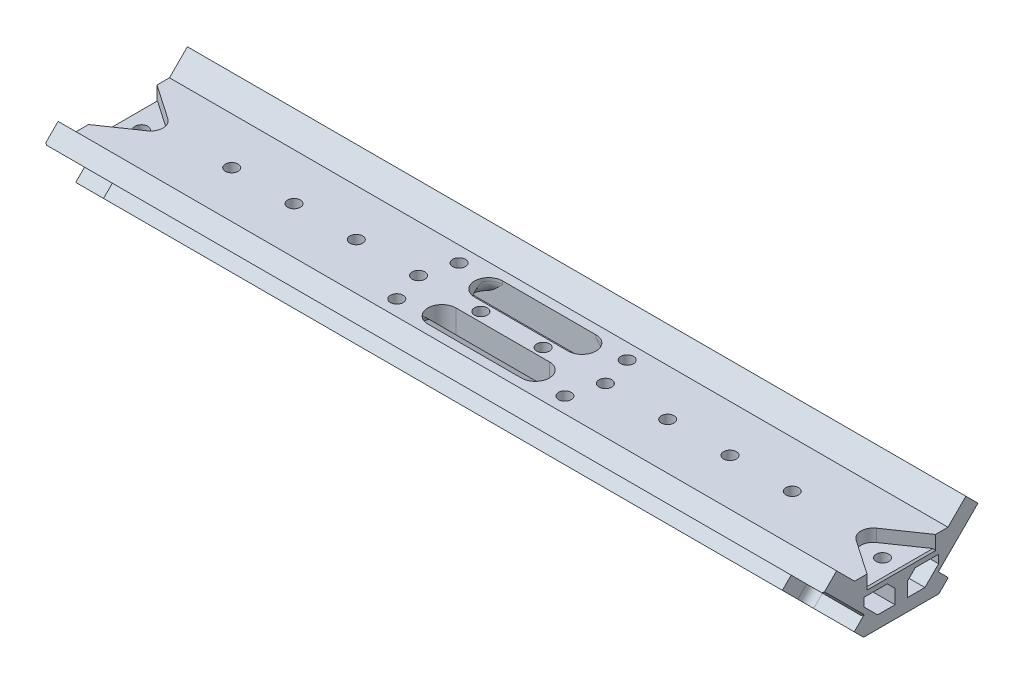
SolidWorks part; units mm, degrees
ref_plane "Front Plane" through (0, 0, 0) normal (0, 0, 1) x (1, 0, 0)
ref_plane "Top Plane" through (0, 0, 0) normal (0, 1, 0) x (1, 0, 0)
ref_plane "Right Plane" through (0, 0, 0) normal (1, 0, 0) x (0, 0, -1)
sketch "Sketch1" plane through (0, 0, 0) normal (1, 0, 0) x (0, 0, -1)
  line L1 (-25, 0) -> (25, 0)
  line L2 (-25, 0) -> (-25, 30)
  line L3 (-25, 30) -> (25, 30)
  line L4 (25, 0) -> (25, 30)
  dimension "D1" = 30
  dimension "D2" = 50
  dimension "D3" = 25
extrude "Boss-Extrude1" add sketch "Sketch1" along normal blind 125 and the other way blind 125
sketch "Sketch2" plane through (125, 0, 0) normal (1, 0, 0) x (0, 0, -1)
  line L0 (-10, 0) -> (-25, 15)
  line L1 (-25, 0) -> (25, 0) construction
  line L2 (-25, 30) -> (-25, 0) construction
  line L3 (-25, 15) -> (-25, 0)
  line L4 (-25, 0) -> (-10, 0)
  line L5 (25, 15) -> (10, 0)
  line L6 (25, 0) -> (25, 30) construction
  line L7 (10, 0) -> (25, 0)
  line L8 (25, 0) -> (25, 15)
  dimension "D1" = 15
  dimension "D2" = 15
  dimension "D3" = 15
  dimension "D4" = 15
extrude "Cut-Extrude1" cut sketch "Sketch2" against normal through all
sketch "Sketch4" plane through (125, 0, 0) normal (1, 0, 0) x (0, 0, -1)
  line L8 (-22.1716, 12.1716) -> (-19.3431, 15)
  line L9 (-10, 0) -> (-25, 15) construction
  line L10 (-19.3431, 15) -> (-25, 20.6569)
  line L11 (-25, 30) -> (-25, 15) construction
  line L12 (-25, 20.6569) -> (-25, 15)
  line L13 (-25, 15) -> (-22.1716, 12.1716)
  line L14 (22.1716, 12.1716) -> (19.3431, 15)
  line L15 (25, 15) -> (10, 0) construction
  line L16 (19.3431, 15) -> (25, 20.6569)
  line L17 (25, 15) -> (25, 30) construction
  line L18 (25, 20.6569) -> (25, 15)
  line L19 (25, 15) -> (22.1716, 12.1716)
  dimension "D1" = 4
  dimension "D2" = 4
  dimension "D3" = 8
  dimension "D4" = 8
extrude "Cut-Extrude2" cut sketch "Sketch4" against normal through all
sketch "Sketch5" plane through (125, 0, 0) normal (1, 0, 0) x (0, 0, -1)
  line L0 (-25, 20.6569) -> (-20.7574, 24.8995)
  line L1 (-20.7574, 24.8995) -> (-15, 19.1421)
  line L2 (-15, 19.1421) -> (15, 19.1421)
  line L3 (15, 19.1421) -> (20.7574, 24.8995)
  line L4 (20.7574, 24.8995) -> (25, 20.6569)
  line L5 (25, 20.6569) -> (25, 30)
  line L6 (25, 30) -> (-25, 30)
  line L7 (-25, 30) -> (-25, 20.6569)
  line L8 (25, 20.6569) -> (19.3431, 15) construction
  point P6 (20.5583, 24.6906)
  point P18 (-20.7574, 24.8995)
  dimension "D1" = 6
  dimension "D2" = 6
  dimension "D3" = 30
  dimension "D4" = 15
extrude "Cut-Extrude3" cut sketch "Sketch5" against normal through all
sketch "Sketch6" plane through (0, 19.1421, 0) normal (0, 1, 0) x (1, 0, 0)
  circle A0 centre (-10, 0) radius 2.05
  circle A1 centre (10, 0) radius 2.05
  circle A2 centre (30, 0) radius 2.05
  circle A3 centre (50, 0) radius 2.05
  circle A4 centre (70, 0) radius 2.05
  circle A5 centre (90, 0) radius 2.05
  circle A6 centre (-30, 0) radius 2.05
  circle A7 centre (-50, 0) radius 2.05
  circle A8 centre (-70, 0) radius 2.05
  circle A9 centre (-90, 0) radius 2.05
  dimension "D1" = 4.1
  dimension "D2" = 20
  dimension "D3" = 10
  dimension "D4" = 20
  dimension "D5" = 20
  dimension "D6" = 20
  dimension "D7" = 20
  dimension "D8" = 20
  dimension "D9" = 20
  dimension "D10" = 20
  dimension "D11" = 20
extrude "Cut-Extrude4" cut sketch "Sketch6" against normal blind 6
sketch "Sketch7" plane through (-125, 0, 0) normal (-1, 0, 0) x (0, 0, 1)
  line L0 (-8.3431, 4) -> (-2, 4)
  line L1 (8.3431, 4) -> (14.9902, 10.647)
  line L3 (10.4951, 15.1421) -> (6.4951, 15.1421)
  line L5 (-14.9902, 10.647) -> (-8.3431, 4)
  line L6 (10, 0) -> (22.1716, 12.1716) construction
  line L7 (-22.1716, 12.1716) -> (-10, 0) construction
  line L8 (10, 0) -> (-10, 0) construction
  line L9 (-2, 10.647) -> (-2, 4)
  line L10 (2, 10.647) -> (2, 4)
  line L11 (-6.4951, 15.1421) -> (-10.4951, 15.1421)
  line L12 (2, 4) -> (8.3431, 4)
  line L13 (-6.4951, 15.1421) -> (-2, 10.647)
  line L14 (-14.9902, 10.647) -> (-10.4951, 15.1421)
  line L15 (14.9902, 10.647) -> (10.4951, 15.1421)
  line L16 (6.4951, 15.1421) -> (2, 10.647)
  line L17 (15, 19.1421) -> (-15, 19.1421) construction
  point P2 (0, 0)
  point P4 (0, 0)
  point P12 (14.8624, 10.5192)
  point P13 (-6.2846, 15.1421)
  point P25 (14.3409, 9.9978)
  dimension "D1" = 2
  dimension "D2" = 4
  dimension "D3" = 4
  dimension "D4" = 4
  dimension "D5" = 90
  dimension "D6" = 90
  dimension "D7" = 2
  dimension "D8" = 135
  dimension "D9" = 4
  dimension "D10" = 4
extrude "Cut-Extrude5" cut sketch "Sketch7" against normal through all
sketch "Sketch8" plane through (-125, 0, 0) normal (-1, 0, 0) x (0, 0, 1)
  line L0 (-12, 13.6372) -> (-12, 7.6569)
  line L1 (-10.4951, 15.1421) -> (-14.9902, 10.647) construction
  line L2 (-14.9902, 10.647) -> (-8.3431, 4) construction
  line L3 (-12, 7.6569) -> (-14.9902, 10.647)
  line L4 (-14.9902, 10.647) -> (-12, 13.6372)
  line L5 (12, 13.6372) -> (12, 7.6569)
  line L6 (14.9902, 10.647) -> (10.4951, 15.1421) construction
  line L7 (8.3431, 4) -> (14.9902, 10.647) construction
  line L8 (12, 7.6569) -> (14.9902, 10.647)
  line L9 (14.9902, 10.647) -> (12, 13.6372)
  point P6 (0, 0)
  dimension "D1" = 12
extrude "Boss-Extrude2" add sketch "Sketch8" against normal through all
sketch "Sketch9" plane through (125, 0, 0) normal (1, 0, 0) x (0, 0, -1)
  line L0 (-16.0858, 6.0858) -> (16.0858, 6.0858)
  line L1 (-10, 0) -> (-22.1716, 12.1716) construction
  line L2 (22.1716, 12.1716) -> (10, 0) construction
  line L3 (16.0858, 6.0858) -> (10, 0)
  line L4 (10, 0) -> (-10, 0)
  line L5 (-10, 0) -> (-16.0858, 6.0858)
extrude "Boss-Extrude3" add sketch "Sketch9" against normal through all
sketch "Sketch10" plane through (125, 0, 0) normal (1, 0, 0) x (0, 0, -1)
  line L0 (-12.0858, 2.0858) -> (12.0858, 2.0858)
  line L1 (-10, 0) -> (-22.1716, 12.1716) construction
  line L2 (22.1716, 12.1716) -> (10, 0) construction
  line L3 (12.0858, 2.0858) -> (10, 0)
  line L4 (10, 0) -> (-10, 0)
  line L5 (-10, 0) -> (-12.0858, 2.0858)
  line L6 (-2, 6.0858) -> (-10.4289, 6.0858) construction
  dimension "D1" = 4
extrude "Cut-Extrude6" cut sketch "Sketch10" against normal through all
sketch "Sketch11" plane through (0, -5, 5) normal (0, -0.7071, 0.7071) x (1, 0, 0)
  line L0 (125, 14.2843) -> (109, 14.2843)
  line L1 (125, 10.0208) -> (125, 24.2843) construction
  line L2 (109, 14.2843) -> (109, 24.2843)
  line L3 (-125, 24.2843) -> (125, 24.2843) construction
  line L4 (109, 24.2843) -> (125, 24.2843)
  line L5 (125, 24.2843) -> (125, 14.2843)
  line L6 (-125, 10.0208) -> (-125, 24.2843) construction
  line L7 (-125, 14.2843) -> (-109, 14.2843)
  line L8 (-125, 14.2843) -> (-125, 24.2843)
  line L9 (-125, 24.2843) -> (-109, 24.2843)
  line L10 (-109, 14.2843) -> (-109, 24.2843)
  line L11 (-125, 24.2843) -> (125, 24.2843) construction
  point P17 (0, 0)
  dimension "D1" = 10
  dimension "D2" = 16
  dimension "D3" = 16
extrude "Cut-Extrude7" cut sketch "Sketch11" against normal up to surface (4 mm away) up to face at (0, 17.8284, 22.1716)
sketch "Sketch12" plane through (0, -5, -5) normal (0, -0.7071, -0.7071) x (-1, 0, 0)
  line L13 (125, 32.2843) -> (-125, 32.2843) construction
  line L18 (-125, 14.2843) -> (-109, 14.2843)
  line L19 (-125, 14.2843) -> (-125, 32.2843)
  line L20 (-125, 32.2843) -> (-109, 32.2843)
  line L21 (-109, 14.2843) -> (-109, 32.2843)
  line L23 (125, 14.2843) -> (109, 14.2843)
  line L24 (125, 14.2843) -> (125, 32.2843)
  line L25 (125, 32.2843) -> (109, 32.2843)
  line L26 (109, 14.2843) -> (109, 32.2843)
  point P15 (0, 0)
  point P18 (-106.5228, 15.2998)
  point P19 (-125, 15.2998)
  point P20 (0, 0)
  point P21 (125, 32.2843)
  point P23 (-125, 32.2843)
  dimension "D1" = 10
  dimension "D2" = 16
  dimension "D3" = 16
extrude "Cut-Extrude11" cut sketch "Sketch12" against normal up to surface (4 mm away) up to face at (0, 17.8284, -22.1716)
sketch "Sketch13" plane through (125, 0, 0) normal (1, 0, 0) x (0, 0, -1)
  line L0 (7.6005, 6.0858) -> (13.5147, 12)
  line L1 (10.4289, 6.0858) -> (2, 6.0858) construction
  line L2 (13.5147, 12) -> (14.9289, 10.5858)
  line L3 (12.2721, 7.9289) -> (19.3431, 15) construction
  line L4 (14.9289, 10.5858) -> (10.4289, 6.0858)
  line L5 (10.4289, 6.0858) -> (7.6005, 6.0858)
  line L6 (-7.6005, 6.0858) -> (-13.5147, 12)
  line L7 (-2, 6.0858) -> (-10.4289, 6.0858) construction
  line L8 (-13.5147, 12) -> (-14.9289, 10.5858)
  line L9 (-19.3431, 15) -> (-12.2721, 7.9289) construction
  line L10 (-14.9289, 10.5858) -> (-10.4289, 6.0858)
  line L11 (-10.4289, 6.0858) -> (-7.6005, 6.0858)
  point P13 (0, 0)
  dimension "D1" = 2
  dimension "D2" = 2
  dimension "D3" = 12
extrude "Boss-Extrude4" add sketch "Sketch13" against normal through all
sketch "Sketch14" plane through (0, 19.1421, 0) normal (0, 1, 0) x (1, 0, 0)
  line L13 (125, 11) -> (109, 0)
  line L14 (125, -15) -> (125, 15) construction
  line L15 (109, 0) -> (125, -11)
  line L16 (125, -11) -> (125, 11)
  line L17 (-125, 11) -> (-109, 0)
  line L18 (-125, -15) -> (-125, 15) construction
  line L19 (-109, 0) -> (-125, -11)
  line L20 (-125, -11) -> (-125, 11)
  point P10 (-125, -8.6578)
  point P13 (0, 0)
  point P16 (0, 0)
  dimension "D1" = 4
  dimension "D2" = 4
  dimension "D3" = 16
extrude "Cut-Extrude12" cut sketch "Sketch14" against normal blind 4
sketch "Sketch15" plane through (-125, 0, 0) normal (-1, 0, 0) x (0, 0, 1)
  line L1 (-15, 15.1421) -> (15, 15.1421)
  line L2 (-15, 15.1421) -> (-15, 13.1421)
  line L3 (-15, 13.1421) -> (15, 13.1421)
  line L4 (15, 15.1421) -> (15, 13.1421)
  point P5 (0, 0)
  point P6 (-13.7129, 15.1683)
  dimension "D1" = 2
  dimension "D2" = 4
  dimension "D3" = 30
  dimension "D4" = 15
extrude "Boss-Extrude5" add sketch "Sketch15" against normal through all
fillet "Fillet1" radius 4 2 edges at (109, 17.1421, 0) (-109, 17.1421, 0)
fillet "Fillet2" radius 3 4 edges at (109, 6.5147, -13.6863) (-109, 6.5147, -13.6863) (-109, 6.5147, 13.6863) (109, 6.5147, 13.6863)
sketch "Sketch16" plane through (0, 15.1421, 0) normal (0, 1, 0) x (1, 0, 0)
  circle A0 centre (119, 0) radius 2.05
  circle A1 centre (-119, 0) radius 2.05
  point P4 (0, 0)
  dimension "D1" = 4.1
  dimension "D2" = 6
  dimension "D3" = 6
extrude "Cut-Extrude13" cut sketch "Sketch16" against normal blind 6
sketch "Sketch17" plane through (0, -2.1716, -2.1716) normal (0, -0.7071, -0.7071) x (-1, 0, 0)
  circle A0 centre (-115, 19.2843) radius 2.05
  circle A1 centre (115, 19.2843) radius 2.05
  point P4 (0, 0)
  dimension "D1" = 4.1
  dimension "D2" = 5
  dimension "D3" = 10
  dimension "D4" = 10
extrude "Cut-Extrude14" cut sketch "Sketch17" against normal blind 6
sketch "Sketch18" plane through (0, -2.1716, 2.1716) normal (0, -0.7071, 0.7071) x (1, 0, 0)
  circle A0 centre (-115, 19.2843) radius 2.05
  circle A1 centre (115, 19.2843) radius 2.05
  point P4 (0, 0)
  dimension "D1" = 4.1
  dimension "D2" = 10
  dimension "D3" = 10
  dimension "D4" = 5
extrude "Cut-Extrude15" cut sketch "Sketch18" against normal blind 6
sketch "Sketch19" plane through (0, -2.1716, -2.1716) normal (0, -0.7071, -0.7071) x (-1, 0, 0)
  circle A0 centre (0, 29.2843) radius 2.05
  circle A1 centre (-60, 29.2843) radius 2.05
  circle A2 centre (-120, 29.2843) radius 2.05
  circle A3 centre (60, 29.2843) radius 2.05
  circle A4 centre (120, 29.2843) radius 2.05
  point P10 (0, 0)
  point P11 (0, 0)
  dimension "D1" = 4.1
  dimension "D2" = 3
  dimension "D3" = 60
  dimension "D4" = 60
  dimension "D5" = 60
  dimension "D6" = 60
extrude "Cut-Extrude16" cut sketch "Sketch19" against normal blind 4
sketch "Sketch20" plane through (0, -2.1716, 2.1716) normal (0, -0.7071, 0.7071) x (1, 0, 0)
  circle A0 centre (0, 29.2843) radius 2.05
  circle A1 centre (60, 29.2843) radius 2.05
  circle A2 centre (120, 29.2843) radius 2.05
  circle A3 centre (-60, 29.2843) radius 2.05
  circle A4 centre (-120, 29.2843) radius 2.05
  point P10 (0, 0)
  point P13 (0, 0)
  dimension "D6" = 4.1
  dimension "D1" = 3
  dimension "D2" = 60
  dimension "D3" = 60
  dimension "D4" = 60
  dimension "D5" = 60
extrude "Cut-Extrude17" cut sketch "Sketch20" against normal blind 4
sketch "Sketch21" plane through (0, 19.1421, 0) normal (0, 1, 0) x (1, 0, 0)
  circle A2 centre (27, 10) radius 2.0518
  circle A3 centre (-27, 10) radius 2.0518
  circle A4 centre (-27, -10) radius 2.0518
  circle A7 centre (27, -10) radius 2.0518
  point P0 (0, 0)
  dimension "D4" = 4.1036
  dimension "D1" = 54
  dimension "D2" = 27
  dimension "D3" = 20
  dimension "D5" = 10
extrude "Cut-Extrude18" cut sketch "Sketch21" against normal blind 6
sketch "Sketch22" plane through (0, 19.1421, 0) normal (0, 1, 0) x (1, 0, 0)
  line L0 (-15, 7.5) -> (15, 7.5) construction
  line L1 (-15, 12) -> (15, 12)
  line L2 (-15, 3) -> (15, 3)
  line L3 (-15, -7.5) -> (15, -7.5) construction
  line L4 (-15, -3) -> (15, -3)
  line L5 (-15, -12) -> (15, -12)
  arc A0 (-15, 12) -> (-15, 3) centre (-15, 7.5) ccw
  arc A1 (15, 3) -> (15, 12) centre (15, 7.5) ccw
  arc A2 (-15, -3) -> (-15, -12) centre (-15, -7.5) ccw
  arc A3 (15, -12) -> (15, -3) centre (15, -7.5) ccw
  point P2 (0, 7.5)
  point P7 (0, -7.5)
  point P14 (17.5563, -7.5835)
  point P15 (0, 0)
  point P17 (13.0131, -3)
  point P18 (0, 0)
  dimension "D1" = 4.5
  dimension "D4" = 30
  dimension "D2" = 15
  dimension "D3" = 7.5
  dimension "D5" = 15
extrude "Cut-Extrude19" cut sketch "Sketch22" against normal blind 8
fillet "Fillet3" radius 5 4 edges at (-19.1093, 13.1421, 9.3341) (19.1093, 13.1421, 9.3341) (19.1093, 13.1421, -9.3341) (-19.1093, 13.1421, -9.3341)
chamfer "Chamfer2" distance 0.5 angle 45 6 edges at (125, 15.1421, 0) (125, 14.2929, 18.636) (125, 14.2929, -18.636) (-125, 15.1421, 0) (-125, 14.2929, 18.636) (-125, 14.2929, -18.636)
